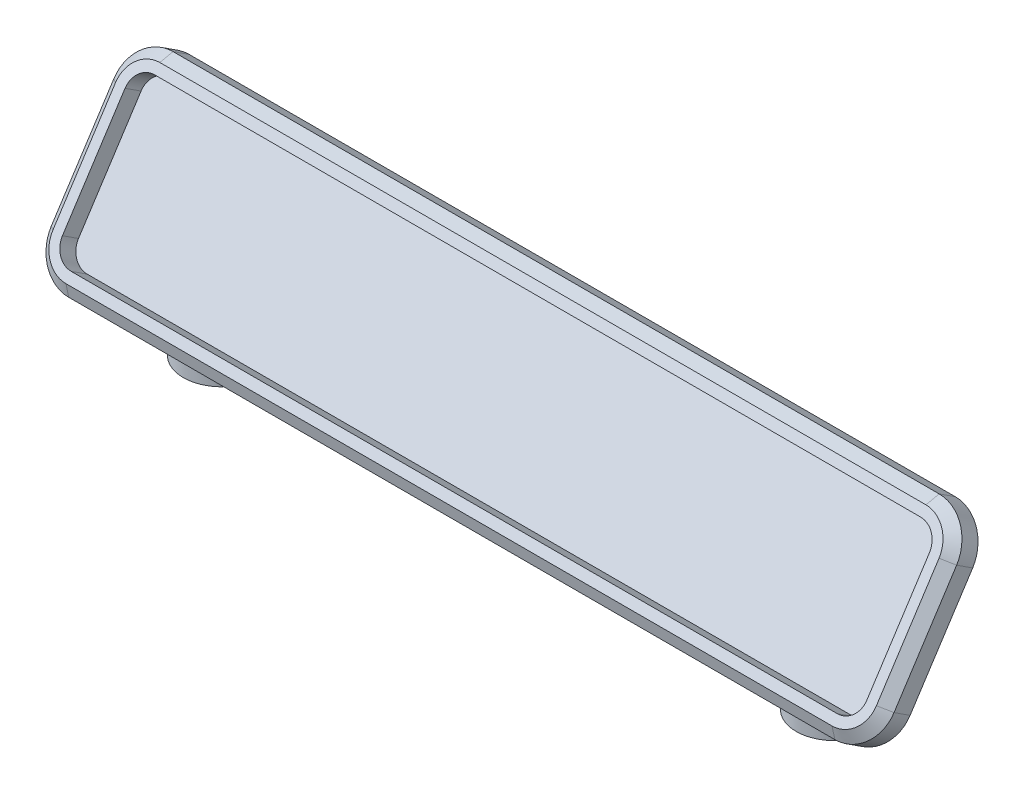
SolidWorks part; units mm, degrees
note: '?' marks a value the reader was unsure of.
ref_plane "Front Plane" through (0, 0, 0) normal (0, 0, 1) x (1, 0, 0)
ref_plane "Top Plane" through (0, 0, 0) normal (0, 1, 0) x (1, 0, 0)
ref_plane "Right Plane" through (0, 0, 0) normal (1, 0, 0) x (0, 0, -1)
sketch "Sketch2" plane through (0, 0, 0) normal (0, 1, 0) x (1, 0, 0)
  line L0 (50.8, 0) -> (-50.8, 0) construction
  circle A0 centre (-50.8, 0) radius 6.35
  circle A1 centre (50.8, 0) radius 6.35
  point P8 (0, 0)
  dimension "D2" = 12.7
  dimension "D1" = 101.6
extrude "Boss-Extrude1" add sketch "Sketch2" along normal blind 19.05
ref_plane "Plane1" through (0, 19.05, 0) normal (0, 1, 0) x (1, 0, 0)
ref_axis "Axis1" through (88.99, 19.05, 0) along (-1, 0, 0)?
ref_plane "Plane2" through (0, 5.6508, 8.7015) normal (0, 0.5446, 0.8387) x (-1, 0, 0)
sketch "Sketch3" plane through (0, 5.6508, 8.7015) normal (0, 0.5446, 0.8387) x (-1, 0, 0)
  line L0 (-50.8, -15.9767) -> (50.8, -15.9767)
  line L2 (-63.5, -31.8517) -> (63.5, -31.8517)
  line L3 (-69.85, -25.5017) -> (-69.85, -6.4517)
  line L4 (-63.5, -0.1017) -> (63.5, -0.1017)
  line L5 (69.85, -25.5017) -> (69.85, -6.4517)
  line L6 (-69.85, -31.8517) -> (69.85, -0.1017) construction
  line L7 (-69.85, -0.1017) -> (69.85, -31.8517) construction
  arc A0 (-63.5, -31.8517) -> (-69.85, -25.5017) centre (-63.5, -25.5017) cw
  arc A1 (63.5, -31.8517) -> (69.85, -25.5017) centre (63.5, -25.5017) ccw
  arc A2 (63.5, -0.1017) -> (69.85, -6.4517) centre (63.5, -6.4517) cw
  arc A3 (-69.85, -6.4517) -> (-63.5, -0.1017) centre (-63.5, -6.4517) cw
  ellipse E0 centre (50.8, -15.9767) end of major axis (44.45, -15.9767) minor radius 3.4585 construction
  ellipse E1 centre (-50.8, -15.9767) end of major axis (-57.15, -15.9767) minor radius 3.4585 construction
  ellipse E2 centre (50.8, -15.9767) end of major axis (44.45, -15.9767) minor radius 3.4585 construction
  ellipse E3 centre (-50.8, -15.9767) end of major axis (-57.15, -15.9767) minor radius 3.4585 construction
  point P22 (0, -15.9767)
  dimension "D3" = 6.35
  dimension "D1" = 139.7
  dimension "D2" = 31.75
extrude "Boss-Extrude2" add sketch "Sketch3" along normal blind 6.35
sketch "Sketch8" plane through (0, 19.05, 0) normal (0, 1, 0) x (1, 0, 0)
  line L0 (44.45, 0) -> (57.15, 0) construction
  line L1 (-57.15, 0) -> (-44.45, 0) construction
  line L2 (44.45, 0) -> (57.15, 0)
  line L3 (-57.15, 0) -> (-44.45, 0)
  arc A0 (57.15, 0) -> (44.45, 0) centre (50.8, 0) ccw construction
  arc A1 (-44.45, 0) -> (-57.15, 0) centre (-50.8, 0) ccw construction
  arc A2 (57.15, 0) -> (44.45, 0) centre (50.8, 0) ccw
  arc A3 (-44.45, 0) -> (-57.15, 0) centre (-50.8, 0) ccw
extrude "Boss-Extrude3" add sketch "Sketch8" along normal up to next contours L2 A2 | A3 L3
sketch "Sketch9" plane through (0, 9.1093, 14.0271) normal (0, 0.5446, 0.8387) x (1, 0, 0)
  line L8 (63.5, 28.6767) -> (-63.5, 28.6767)
  line L9 (-66.675, 25.5017) -> (-66.675, 6.4517)
  line L10 (-63.5, 3.2767) -> (63.5, 3.2767)
  line L11 (66.675, 6.4517) -> (66.675, 25.5017)
  line L12 (63.5, 28.6767) -> (-63.5, 28.6767)
  line L13 (-66.675, 25.5017) -> (-66.675, 6.4517)
  line L14 (-63.5, 3.2767) -> (63.5, 3.2767)
  line L15 (66.675, 6.4517) -> (66.675, 25.5017)
  arc A8 (63.5, 3.2767) -> (66.675, 6.4517) centre (63.5, 6.4517) ccw
  arc A9 (63.5, 3.2767) -> (66.675, 6.4517) centre (63.5, 6.4517) ccw
  arc A10 (66.675, 25.5017) -> (63.5, 28.6767) centre (63.5, 25.5017) ccw
  arc A11 (66.675, 25.5017) -> (63.5, 28.6767) centre (63.5, 25.5017) ccw
  arc A12 (-63.5, 28.6767) -> (-66.675, 25.5017) centre (-63.5, 25.5017) ccw
  arc A13 (-63.5, 28.6767) -> (-66.675, 25.5017) centre (-63.5, 25.5017) ccw
  arc A14 (-66.675, 6.4517) -> (-63.5, 3.2767) centre (-63.5, 6.4517) ccw
  arc A15 (-66.675, 6.4517) -> (-63.5, 3.2767) centre (-63.5, 6.4517) ccw
  dimension "D1" = 3.175
extrude "Cut-Extrude1" cut sketch "Sketch9" against normal blind 3.175
chamfer "Chamfer2" distance 1.5875 angle 45 16 edges at (-69.85, 19.05, 0) (0, 32.3639, -8.6461) (69.85, 19.05, 0) (0, 5.7361, 8.6461) (0, 9.1946, 13.9717) (-69.85, 22.5085, 5.3256) (69.85, 22.5085, 5.3256) (0, 35.8224, -3.3206) (67.9901, 30.8041, -7.6332) (-67.9901, 30.8041, -7.6332) (67.9901, 7.2959, 7.6332) (-67.9901, 7.2959, 7.6332) (67.9901, 10.7544, 12.9587) (-67.9901, 10.7544, 12.9587) (67.9901, 34.2625, -2.3076) (-67.9901, 34.2625, -2.3076)
hole_wizard "Hole1" positions "3DSketch1" profile "Sketch10" legacy
sketch3d "3DSketch1"
  line L0 (-50.8, 28.8281, 0) -> (-50.8, 0, 0) construction
  line L1 (50.8, 28.8281, 0) -> (50.8, 0, 0) construction
  point P0 (-50.8, 0, 0)
  point P4 (50.8, 0, 0)
sketch "Sketch10" plane through (-50.8, 0, 0) normal (1, 0, 0) x (0, 0, -1)
  line L0 (0, 0) -> (0, 10.16)
  line L1 (0, 10.16) -> (2.8575, 10.16)
  line L2 (2.8575, 10.16) -> (2.8575, 0.6858)
  line L3 (2.8575, 0.6858) -> (3.4925, 0.6858)
  line L4 (3.4925, 0.6858) -> (3.4925, 0)
  line L5 (3.4925, 0) -> (0, 0)
  line L6 (0, 110) -> (0, -10) construction
  dimension "Diameter" = 5.715
  dimension "Depth" = 10.16
  dimension "C-Bore Diameter" = 6.985
  dimension "C-Bore Depth" = 0.6858
